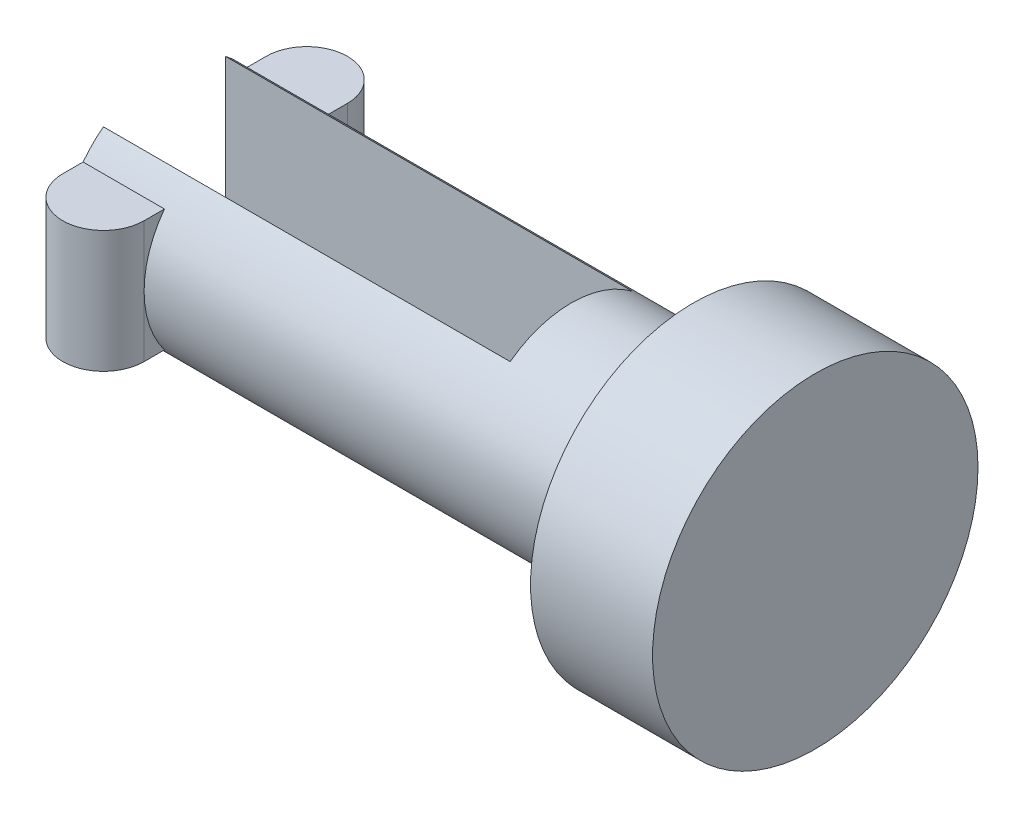
SolidWorks part; units mm, degrees
ref_plane "Front Plane" through (0, 0, 0) normal (0, 0, 1) x (1, 0, 0)
ref_plane "Top Plane" through (0, 0, 0) normal (0, 1, 0) x (1, 0, 0)
ref_plane "Right Plane" through (0, 0, 0) normal (1, 0, 0) x (0, 0, -1)
sketch "Sketch1" plane through (0, 0, 0) normal (1, 0, 0) x (0, 0, -1)
  circle A0 centre (0, 0) radius 4
  circle A1 centre (0, 0) radius 2.5
  dimension "D1" = 5
  dimension "D2" = 8
extrude "Boss-Extrude1" add sketch "Sketch1" along normal blind 3 contours A0
extrude "Boss-Extrude2" add sketch "Sketch1<3>" against normal blind 13 contours A1
sketch "Sketch1<3>" plane through (0, 0, 0) normal (1, 0, 0) x (0, 0, -1) same geometry as "Sketch1"
sketch "Sketch3" plane through (0, 0, 0) normal (0, 1, 0) x (1, 0, 0)
  line L0 (-12, 2.5) -> (-12, -2.5) construction
  line L1 (0, 2.5) -> (-13, 2.5) construction
  line L2 (-13, -2.5) -> (0, -2.5) construction
  line L3 (-11, 2.5) -> (-11, -2.5)
  line L4 (-13, 2.5) -> (-13, -2.5)
  line L5 (-13, 2.5) -> (-13, -2.5) construction
  arc A0 (-11, 2.5) -> (-13, 2.5) centre (-12, 2.5) ccw
  arc A1 (-13, -2.5) -> (-11, -2.5) centre (-12, -2.5) ccw
  point P6 (-12, 0)
  dimension "D1" = 1
extrude "Boss-Extrude3" add sketch "Sketch3" along normal mid plane 3 contours A0 L4 A1 L3
sketch "Sketch2" plane through (0, 0, 0) normal (0, 1, 0) x (1, 0, 0)
  line L0 (-13, 0) -> (-9.1208, 0) construction
  line L1 (-13, 2.5) -> (-13, -2.5) construction
  line L2 (-13, 1.5) -> (-13, -1.5)
  line L3 (-13, 1.5) -> (-3, 1.5)
  line L4 (-13, -1.5) -> (-3, -1.5)
  line L5 (-3, 1.5) -> (-3, -1.5)
  dimension "D1" = 10
  dimension "D2" = 3
extrude "Cut-Extrude1" cut sketch "Sketch2" against normal through all both and the other way through all
